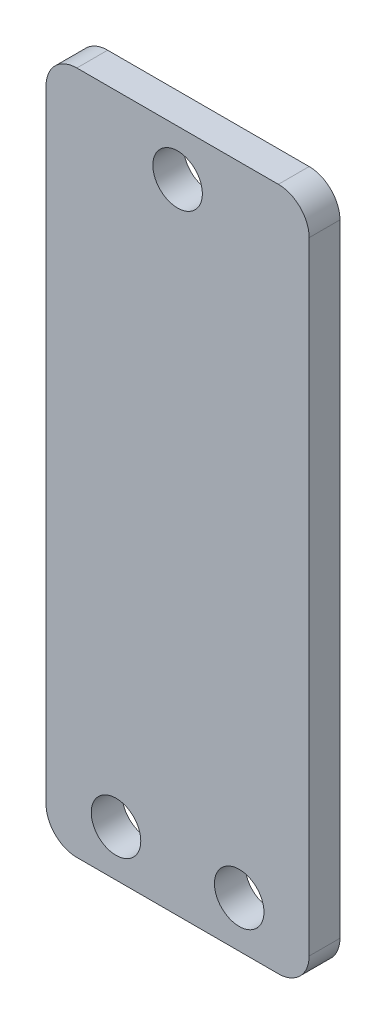
SolidWorks part; units mm, degrees
ref_plane "Front Plane" through (0, 0, 0) normal (0, 0, 1) x (1, 0, 0)
ref_plane "Top Plane" through (0, 0, 0) normal (0, 1, 0) x (1, 0, 0)
ref_plane "Right Plane" through (0, 0, 0) normal (1, 0, 0) x (0, 0, -1)
sketch "Sketch1" plane through (0, 0, 0) normal (0, 0, 1) x (1, 0, 0)
  line L0 (8.9027, -4.6609) -> (-8.9027, -4.6609) construction
  line L1 (10.3886, -4.6609) -> (-10.3886, -4.6609)
  line L2 (13.5636, -1.4859) -> (13.5636, 62.6618)
  line L3 (10.3886, 65.8368) -> (-10.3886, 65.8368)
  line L4 (-13.5636, -1.4859) -> (-13.5636, 62.6618)
  line L5 (69.2801, 65.8368) -> (24.8301, 65.8368) construction
  arc A0 (8.9027, -4.6609) -> (8.9027, 4.6609) centre (8.9027, 0) ccw construction
  arc A1 (-8.9027, 4.6609) -> (-8.9027, -4.6609) centre (-8.9027, 0) ccw construction
  arc A2 (13.5636, 62.6618) -> (10.3886, 65.8368) centre (10.3886, 62.6618) ccw
  arc A3 (-10.3886, 65.8368) -> (-13.5636, 62.6618) centre (-10.3886, 62.6618) ccw
  arc A4 (-10.3886, -4.6609) -> (-13.5636, -1.4859) centre (-10.3886, -1.4859) cw
  arc A5 (10.3886, -4.6609) -> (13.5636, -1.4859) centre (10.3886, -1.4859) ccw
  dimension "D1" = 3.175
extrude "Boss-Extrude1" add sketch "Sketch1" along normal blind 3.175
hole_wizard "#10 Clearance Hole1" positions "Sketch2" profile "Sketch3" hole size "#10" standard "ANSI Inch" end condition through all
sketch "Sketch2" plane through (0, 0, 3.175) normal (0, 0, 1) x (1, 0, 0)
  line L0 (6.35, 0.1016) -> (-6.35, 0.1016) construction
  line L2 (-10.3886, -4.6609) -> (10.3886, -4.6609) construction
  line L3 (10.3886, 65.8368) -> (-10.3886, 65.8368) construction
  point P0 (6.35, 0.1016)
  point P2 (-6.35, 0.1016)
  point P4 (0, 61.0743)
  point P11 (0, 0.1016)
  point P14 (0, -4.6609)
  point P18 (0, 65.8368)
  dimension "D1" = 12.7
  dimension "D2" = 4.7625
  dimension "D3" = 4.7625
sketch "Sketch3" plane through (6.35, 0.1016, 3.175) normal (1, 0, 0) x (0, -1, 0)
  line L0 (0, 0) -> (0, 3.175)
  line L1 (0, 3.175) -> (2.5527, 3.175)
  line L2 (2.5527, 3.175) -> (2.5527, 0)
  line L5 (2.5527, 0) -> (0, 0)
  line L11 (0, -6.35) -> (0, 107.95) construction
  dimension "Thru Hole Dia." = 5.1054
  dimension "Thru Hole Depth" = 3.175
